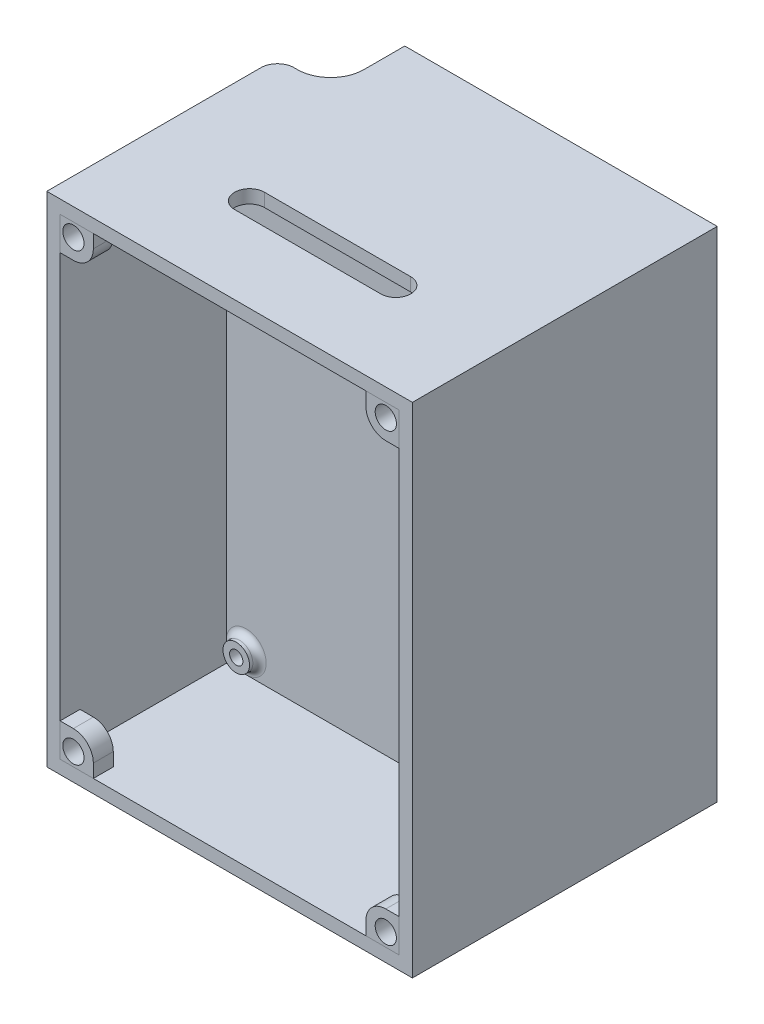
SolidWorks part; units mm, degrees
ref_plane "Front Plane" through (0, 0, 0) normal (1, 0, 0) x (0, 1, 0)
ref_plane "Top Plane" through (0, 0, 0) normal (0, 0, 1) x (0, 1, 0)
ref_plane "Right Plane" through (0, 0, 0) normal (0, 1, 0) x (-1, 0, 0)
sketch "Sketch1" plane through (0, 0, 0) normal (0, 0, 1) x (0, 1, 0)
  line L7 (-37.5, -27.5) -> (37.5, -27.5)
  line L8 (-37.5, -27.5) -> (-37.5, 27.5)
  line L9 (-37.5, 27.5) -> (37.5, 27.5)
  line L10 (37.5, -27.5) -> (37.5, 27.5)
  point P0 (0, 0)
  point P10 (0, 0)
  dimension "D4" = 55
  dimension "D5" = 75
extrude "Boss-Extrude1" add sketch "Sketch1" along normal blind 3
sketch "Sketch2" plane through (0, 0, 3) normal (0, 0, 1) x (1, 0, 0)
  line L1 (22.5, -32.5) -> (-22.5, -32.5)
  line L2 (22.5, -32.5) -> (22.5, 32.5)
  line L3 (22.5, 32.5) -> (-22.5, 32.5)
  line L4 (-22.5, -32.5) -> (-22.5, 32.5)
  line L5 (22.5, -32.5) -> (-22.5, 32.5) construction
  line L6 (22.5, 32.5) -> (-22.5, -32.5) construction
  circle A0 centre (-22.5, 32.5) radius 1
  circle A1 centre (22.5, 32.5) radius 1
  circle A2 centre (-22.5, -32.5) radius 1
  circle A3 centre (22.5, -32.5) radius 1
  point P0 (0, 0)
  dimension "D3" = 2
  dimension "D1" = 45
  dimension "D2" = 65
extrude "Cut-Extrude1" cut sketch "Sketch2" against normal through all draft 5 contours A2 | A0 | A1 | A3
sketch "Sketch3" plane through (0, 0, 3) normal (0, 0, 1) x (1, 0, 0)
  line L0 (25.5, 35.5) -> (-25.5, 35.5)
  line L1 (-25.5, 35.5) -> (-25.5, -35.5)
  line L2 (-25.5, -35.5) -> (25.5, -35.5)
  line L3 (25.5, -35.5) -> (25.5, 35.5)
  line L4 (27.5, 37.5) -> (-27.5, 37.5)
  line L5 (-27.5, 37.5) -> (-27.5, -37.5)
  line L6 (-27.5, -37.5) -> (27.5, -37.5)
  line L7 (27.5, -37.5) -> (27.5, 37.5)
  line L8 (27.5, 37.5) -> (-27.5, 37.5)
  line L9 (-27.5, 37.5) -> (-27.5, -37.5)
  line L10 (-27.5, -37.5) -> (27.5, -37.5)
  line L11 (27.5, -37.5) -> (27.5, 37.5)
  dimension "D1" = 0
  dimension "D2" = 2
extrude "Boss-Extrude2" add sketch "Sketch3" along normal blind 25
ref_plane "Plane1" through (0, 0, 28) normal (0, 0, 1) x (0, -1, 0)
sketch "Sketch4" plane through (0, 0, 28) normal (0, 0, 1) x (0, -1, 0)
  line L0 (-37.5, 0) -> (37.5, 0) construction
  line L1 (-35.5, 25.5) -> (-30.5, 25.5)
  line L2 (-35.5, 25.5) -> (-35.5, 20.5)
  line L3 (-35.5, 20.5) -> (-33.5, 20.5)
  line L4 (-30.5, 25.5) -> (-30.5, 23.5)
  line L5 (-37.5, 27.5) -> (-37.5, -27.5) construction
  line L6 (37.5, -27.5) -> (37.5, 27.5) construction
  line L7 (0, 27.5) -> (0, -27.5) construction
  line L8 (37.5, 27.5) -> (-37.5, 27.5) construction
  line L9 (-37.5, -27.5) -> (37.5, -27.5) construction
  line L10 (35.5, 20.5) -> (33.5, 20.5)
  line L11 (30.5, 25.5) -> (30.5, 23.5)
  line L12 (35.5, 25.5) -> (30.5, 25.5)
  line L13 (35.5, 25.5) -> (35.5, 20.5)
  line L14 (35.5, -25.5) -> (35.5, -20.5)
  line L15 (35.5, -25.5) -> (30.5, -25.5)
  line L16 (30.5, -25.5) -> (30.5, -23.5)
  line L17 (35.5, -20.5) -> (33.5, -20.5)
  line L18 (-35.5, -20.5) -> (-33.5, -20.5)
  line L19 (-30.5, -25.5) -> (-30.5, -23.5)
  line L20 (-35.5, -25.5) -> (-30.5, -25.5)
  line L21 (-35.5, -25.5) -> (-35.5, -20.5)
  arc A0 (-33.5, 20.5) -> (-30.5, 23.5) centre (-33.5, 23.5) ccw
  arc A1 (33.5, 20.5) -> (30.5, 23.5) centre (33.5, 23.5) cw
  arc A2 (33.5, -20.5) -> (30.5, -23.5) centre (33.5, -23.5) ccw
  arc A3 (-33.5, -20.5) -> (-30.5, -23.5) centre (-33.5, -23.5) cw
  point P6 (-30.5, 20.5)
  dimension "D3" = 3
  dimension "D1" = 5
  dimension "D2" = 5
extrude "Boss-Extrude4" add sketch "Sketch4" against normal blind 3 separate body
sketch "Sketch5" plane through (0, 0, 28) normal (0, 0, 1) x (0, -1, 0)
  line L1 (33.5, -23.5) -> (-33.5, -23.5)
  line L2 (33.5, -23.5) -> (33.5, 23.5)
  line L3 (33.5, 23.5) -> (-33.5, 23.5)
  line L4 (-33.5, -23.5) -> (-33.5, 23.5)
  line L5 (33.5, -23.5) -> (-33.5, 23.5) construction
  line L6 (33.5, 23.5) -> (-33.5, -23.5) construction
  circle A0 centre (-33.5, 23.5) radius 1.6
  circle A1 centre (-33.5, -23.5) radius 1.6
  circle A2 centre (33.5, -23.5) radius 1.6
  circle A3 centre (33.5, 23.5) radius 1.6
  point P0 (0, 0)
  dimension "D1" = 3.2
extrude "Cut-Extrude2" cut sketch "Sketch5" against normal up to surface (25 mm away) contours A3 | A2 | A1 | A0 up to face at (0, 0, 3)
sketch "Sketch8" plane through (0, 37.5, 0) normal (0, 1, 0) x (-1, 0, 0)
  line L0 (0, 0) -> (0, 28) construction
  line L1 (-27.5, 28) -> (27.5, 28) construction
  line L5 (-11, 14) -> (11, 14) construction
  line L6 (-11, 16.25) -> (11, 16.25)
  line L7 (-11, 11.75) -> (11, 11.75)
  arc A0 (-11, 16.25) -> (-11, 11.75) centre (-11, 14) ccw
  arc A1 (11, 11.75) -> (11, 16.25) centre (11, 14) ccw
  point P13 (0, 14)
  dimension "D1" = 2.25
  dimension "D2" = 22
extrude "Cut-Extrude4" cut sketch "Sketch8" against normal up to surface (2 mm away) up to face at (0, 35.5, 15.5)
ref_plane "Plane3" through (0, 37.5, 0) normal (0, 1, 0) x (-1, 0, 0)
sketch "Sketch10" plane through (0, 37.5, 0) normal (0, 1, 0) x (-1, 0, 0)
  line L0 (-27.5, 0) -> (27.5, 0)
  line L1 (-27.5, 0) -> (-27.5, -17.8545)
  line L2 (-27.5, -17.8545) -> (19.5, -17.8545)
  line L3 (19.5, -17.8545) -> (19.5, -11.7045)
  line L4 (24.5, -6.7045) -> (25, -6.7045)
  line L5 (27.5, -4.2045) -> (27.5, 0)
  arc A0 (19.5, -11.7045) -> (24.5, -6.7045) centre (24.5, -11.7045) cw
  arc A1 (25, -6.7045) -> (27.5, -4.2045) centre (25, -4.2045) ccw
  dimension "D1" = 5
  dimension "D3" = 2.5
  dimension "D2" = 0.5
  dimension "D4" = 6.15
extrude "Boss-Extrude6" add sketch "Sketch10" against normal up to surface (75 mm away) up to face at (0, -37.5, 14)
sketch "Sketch11" plane through (-19.5, 0, 0) normal (-1, 0, 0) x (0, -1, 0)
  line L0 (0, -17.8545) -> (0, -11.7045) construction
  line L1 (37.5, -17.8545) -> (-37.5, -17.8545) construction
  line L2 (37.5, -11.7045) -> (-37.5, -11.7045) construction
  line L3 (12.5, -14.7795) -> (-12.5, -14.7795) construction
  circle A0 centre (-12.5, -14.7795) radius 2.5
  circle A1 centre (12.5, -14.7795) radius 2.5
  point P9 (0, -14.7795)
  dimension "D2" = 5
  dimension "D1" = 25
extrude "Cut-Extrude5" cut sketch "Sketch11" against normal blind 1.7
sketch "Sketch12" plane through (0, 0, 3) normal (0, 0, 1) x (1, 0, 0)
  circle A0 centre (-22.5, -32.5) radius 1 construction
  circle A1 centre (-22.5, 32.5) radius 1 construction
  circle A2 centre (22.5, 32.5) radius 1 construction
  circle A3 centre (22.5, -32.5) radius 1 construction
  circle A4 centre (-22.5, -32.5) radius 1
  circle A5 centre (-22.5, 32.5) radius 1
  circle A6 centre (22.5, 32.5) radius 1
  circle A7 centre (22.5, -32.5) radius 1
  circle A8 centre (22.5, -32.5) radius 2
  circle A9 centre (22.5, 32.5) radius 2
  circle A10 centre (-22.5, 32.5) radius 2
  circle A11 centre (-22.5, -32.5) radius 2
  dimension "D1" = 1
extrude "Boss-Extrude8" add sketch "Sketch12" along normal blind 1.5
fillet "Fillet2" radius 1 4 edges at (20.5, 32.5, 3) (20.5, -32.5, 3) (-24.5, -32.5, 3) (-24.5, 32.5, 3)
